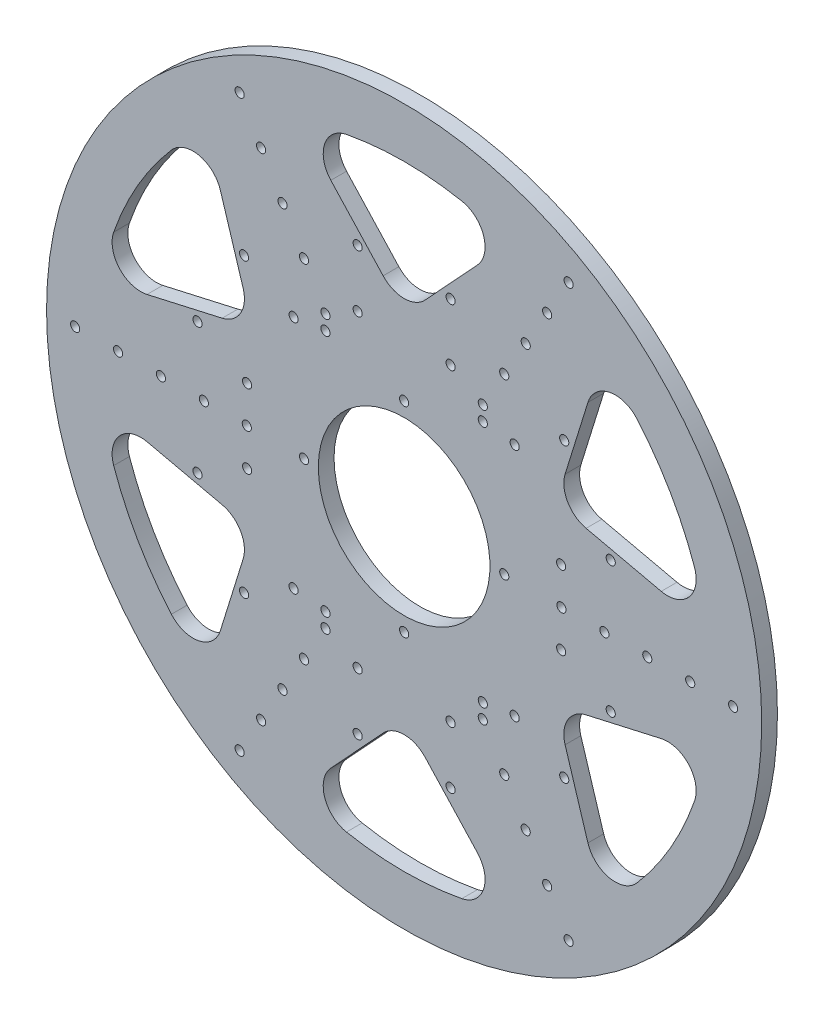
SolidWorks part; units mm, degrees
material "ﾎﾟﾘｴﾁﾚﾝﾃﾚﾌﾀﾗｰﾄ(PET)"
ref_plane "正面" through (0, 0, 0) normal (0, 0, 1) x (1, 0, 0)
ref_plane "平面" through (0, 0, 0) normal (0, 1, 0) x (1, 0, 0)
ref_plane "右側面" through (0, 0, 0) normal (1, 0, 0) x (0, 0, -1)
sketch "ｽｹｯﾁ1" plane through (0, 0, 0) normal (0, 0, 1) x (1, 0, 0)
  circle A0 centre (0, 0) radius 125
  dimension "D1" = 250
extrude "ﾎﾞｽ - 押し出し1" add sketch "ｽｹｯﾁ1" along normal blind 5.5
sketch "ｽｹｯﾁ2" plane through (0, 0, 0) normal (0, 1, 0) x (1, 0, 0)
  line L0 (0, 0) -> (0, -50)
  dimension "D1" = 50
sketch "ｽｹｯﾁ3" plane through (0, 0, 0) normal (0, 0, -1) x (-1, 0, 0)
  line L0 (0, 0) -> (0, 64) construction
  line L1 (0, 0) -> (0, 76) construction
  line L2 (16.25, 54) -> (-16.25, 54) construction
  line L3 (16.25, 54) -> (16.25, 74) construction
  line L4 (16.25, 74) -> (-16.25, 74) construction
  line L5 (-16.25, 54) -> (-16.25, 74) construction
  line L6 (16.25, 54) -> (-16.25, 74) construction
  line L7 (16.25, 74) -> (-16.25, 54) construction
  line L8 (0, 107.5) -> (0, 0) construction
  line L9 (0, 0) -> (36.7672, 101.017) construction
  line L10 (0, 0) -> (-36.7672, 101.017) construction
  line L11 (-25.6298, 88.9783) -> (-7.3405, 69.209)
  line L12 (25.6298, 88.9783) -> (7.3405, 69.209)
  circle A0 centre (-16.25, 74) radius 1.6
  circle A1 centre (-16.25, 54) radius 1.6
  circle A2 centre (16.25, 54) radius 1.6
  circle A3 centre (16.25, 74) radius 1.6
  circle A4 centre (0, 76) radius 10 construction
  circle A5 centre (0, 0) radius 107.5 construction
  arc A6 (-20.1651, 105.5918) -> (20.1651, 105.5918) centre (0, 0) cw
  arc A7 (-7.3405, 69.209) -> (7.3405, 69.209) centre (0, 76) ccw
  arc A8 (-25.6298, 88.9783) -> (-20.1651, 105.5918) centre (-18.2893, 95.7693) cw
  arc A9 (20.1651, 105.5918) -> (25.6298, 88.9783) centre (18.2893, 95.7693) cw
  point P20 (7.5722, 69.444)
  dimension "D4" = 3.2
  dimension "D6" = 20
  dimension "D7" = 215
  dimension "D10" = 10
  dimension "D1" = 54
  dimension "D2" = 32.5
  dimension "D3" = 20
  dimension "D5" = 76
  dimension "D8" = 20
  dimension "D9" = 20
extrude "ｶｯﾄ - 押し出し1" cut sketch "ｽｹｯﾁ3" against normal through all
pattern_circular "円形ﾊﾟﾀｰﾝ1" count 6 over 360 about axis through (0, 0, 0) along (0, 0, 1) of "ｶｯﾄ - 押し出し1"
sketch "ｽｹｯﾁ4" plane through (0, 0, 0) normal (0, 0, -1) x (-1, 0, 0)
  circle A0 centre (0, 0) radius 30
  circle A1 centre (0, 0) radius 35 construction
  circle A2 centre (0, 35) radius 1.6
  circle A3 centre (35, 0) radius 1.6
  circle A4 centre (0, -35) radius 1.6
  circle A5 centre (-35, 0) radius 1.6
  point P6 (33.7343, -9.327)
  point P7 (0, 0)
  point P8 (0, 0)
  point P15 (0, 0)
  dimension "D1" = 60
  dimension "D2" = 70
  dimension "D3" = 3.2
  dimension "D4" = 4
extrude "ｶｯﾄ - 押し出し2" cut sketch "ｽｹｯﾁ4" against normal through all
sketch "ｽｹｯﾁ5" plane through (0, 0, 0) normal (0, 0, -1) x (-1, 0, 0)
  line L1 (27.5, -42.5) -> (-27.5, -42.5) construction
  line L2 (27.5, -42.5) -> (27.5, 42.5) construction
  line L3 (27.5, 42.5) -> (-27.5, 42.5) construction
  line L4 (-27.5, -42.5) -> (-27.5, 42.5) construction
  line L5 (27.5, -42.5) -> (-27.5, 42.5) construction
  line L6 (27.5, 42.5) -> (-27.5, -42.5) construction
  circle A0 centre (-27.5, 42.5) radius 1.6
  circle A1 centre (27.5, 42.5) radius 1.6
  circle A2 centre (-27.5, -42.5) radius 1.6
  circle A3 centre (27.5, -42.5) radius 1.6
  point P0 (0, 0)
  dimension "D3" = 3.2
  dimension "D1" = 55
  dimension "D2" = 85
extrude "ｶｯﾄ - 押し出し3" cut sketch "ｽｹｯﾁ5" against normal through all
sketch "ｽｹｯﾁ6" plane through (0, 0, 0) normal (0, 0, -1) x (-1, 0, 0)
  line L0 (-115, 0) -> (0, 0) construction
  line L1 (-57.5, 99.5929) -> (0, 0) construction
  line L2 (57.5, 99.5929) -> (0, 0) construction
  line L3 (115, 0) -> (0, 0) construction
  line L4 (57.5, -99.5929) -> (0, 0) construction
  line L5 (-57.5, -99.5929) -> (0, 0) construction
  circle A0 centre (0, 0) radius 115 construction
  circle A1 centre (-115, 0) radius 1.6
  circle A2 centre (0, 0) radius 125 construction
  circle A3 centre (-100, 0) radius 1.6
  circle A4 centre (-85, 0) radius 1.6
  circle A5 centre (-70, 0) radius 1.6
  circle A6 centre (-55, 0) radius 1.6
  circle A7 centre (-57.5, 99.5929) radius 1.6
  circle A8 centre (-50, 86.6025) radius 1.6
  circle A9 centre (-42.5, 73.6122) radius 1.6
  circle A10 centre (-35, 60.6218) radius 1.6
  circle A11 centre (-27.5, 47.6314) radius 1.6
  circle A12 centre (57.5, 99.5929) radius 1.6
  circle A13 centre (50, 86.6025) radius 1.6
  circle A14 centre (42.5, 73.6122) radius 1.6
  circle A15 centre (35, 60.6218) radius 1.6
  circle A16 centre (27.5, 47.6314) radius 1.6
  circle A17 centre (115, 0) radius 1.6
  circle A18 centre (100, 0) radius 1.6
  circle A19 centre (85, 0) radius 1.6
  circle A20 centre (70, 0) radius 1.6
  circle A21 centre (55, 0) radius 1.6
  circle A22 centre (57.5, -99.5929) radius 1.6
  circle A23 centre (50, -86.6025) radius 1.6
  circle A24 centre (42.5, -73.6122) radius 1.6
  circle A25 centre (35, -60.6218) radius 1.6
  circle A26 centre (27.5, -47.6314) radius 1.6
  circle A27 centre (-57.5, -99.5929) radius 1.6
  circle A28 centre (-50, -86.6025) radius 1.6
  circle A29 centre (-42.5, -73.6122) radius 1.6
  circle A30 centre (-35, -60.6218) radius 1.6
  circle A31 centre (-27.5, -47.6314) radius 1.6
  point P68 (0, 0)
  dimension "D1" = 3.2
  dimension "D2" = 10
  dimension "D3" = 5
  dimension "D4" = 15
  dimension "D5" = 6
extrude "ｶｯﾄ - 押し出し4" cut sketch "ｽｹｯﾁ6" against normal through all
equation "\"D1@ｽｹｯﾁ3\"=50+4"
equation "\"D7@ｽｹｯﾁ3\"=107.5*2"
equation "\"D9@ｽｹｯﾁ3\"=\"D8@ｽｹｯﾁ3\""
